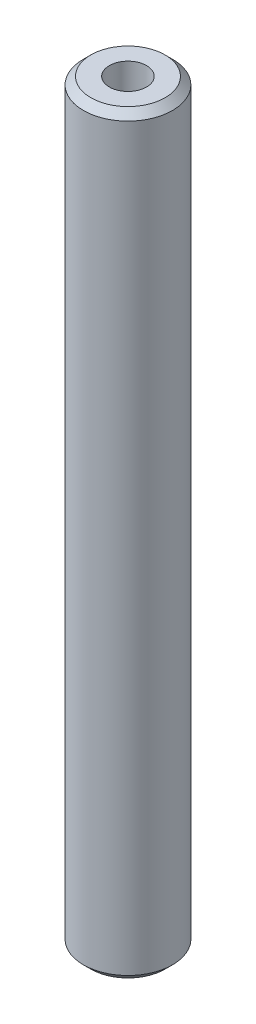
SolidWorks part; units mm, degrees
ref_plane "Front Plane" through (0, 0, 0) normal (0, 0, 1) x (1, 0, 0)
ref_plane "Top Plane" through (0, 0, 0) normal (0, 1, 0) x (1, 0, 0)
ref_plane "Right Plane" through (0, 0, 0) normal (1, 0, 0) x (0, 0, -1)
sketch "Sketch1" plane through (0, 0, 0) normal (0, 1, 0) x (1, 0, 0)
  circle A0 centre (0, 0) radius 7.5
  dimension "SHAFT_OD" = 15
extrude "Boss-Extrude1" add sketch "Sketch1" along normal blind 127.1779
sketch "Sketch2" plane through (0, 0, 0) normal (0, 1, 0) x (1, 0, 0)
  circle A0 centre (0, 0) radius 3.1341
  dimension "BORE_D" = 6.2682
extrude "Cut-Extrude1" cut sketch "Sketch2" along normal through all
chamfer "Chamfer1" distance 1.2429 angle 45 2 edges at (0, 127.1779, 7.5) (0, 0, 7.5)
